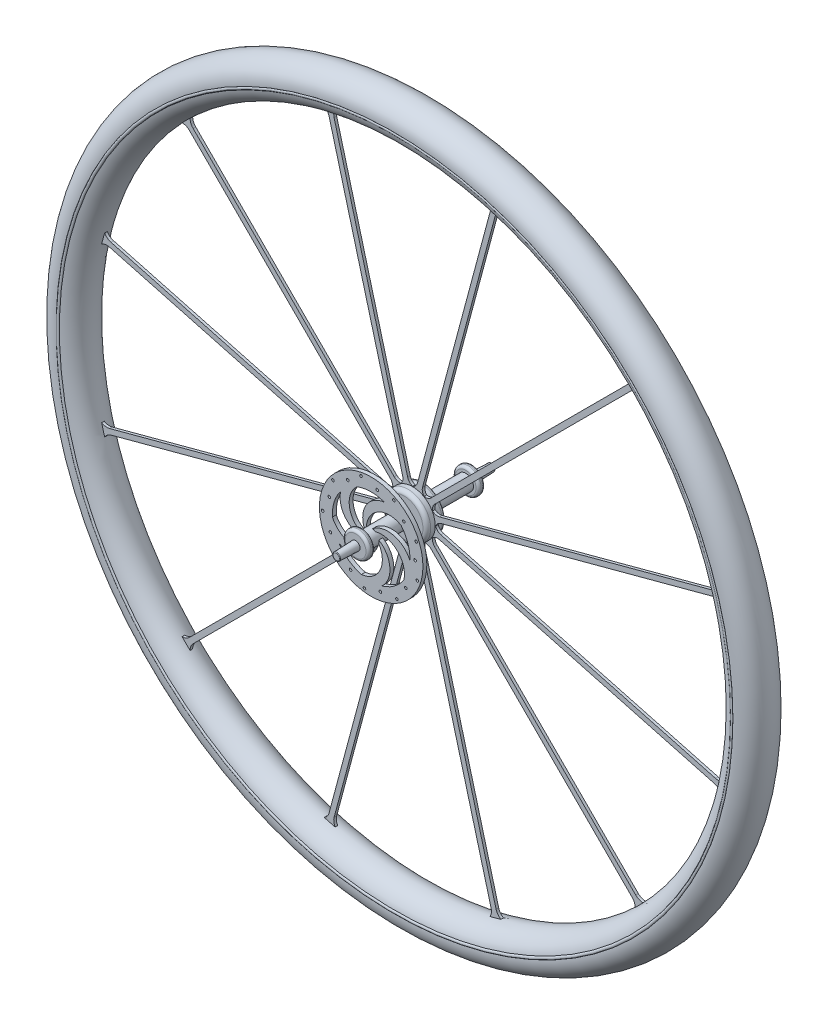
SolidWorks part; units mm, degrees
note: The reader was unsure of these and kept them because the rebuilt part matched: shared geometry of "Sketch1<5>".
ref_plane "Front Plane" through (0, 0, 0) normal (0, 0, 1) x (1, 0, 0)
ref_plane "Top Plane" through (0, 0, 0) normal (0, 1, 0) x (1, 0, 0)
ref_plane "Right Plane" through (0, 0, 0) normal (1, 0, 0) x (0, 0, -1)
sketch "Sketch1" plane through (0, 0, 0) normal (0, 0, 1) x (1, 0, 0)
  circle A2 centre (0, 0) radius 5
  circle A3 centre (0, 0) radius 10
  dimension "D1" = 10
  dimension "D2" = 20
extrude "Boss-Extrude1" add sketch "Sketch1" along normal mid plane 90 contours A3 A2
extrude "Boss-Extrude2" add sketch "Sketch1<5>" along normal mid plane 120 draft 2 contours A2
sketch "Sketch1<5>" plane through (0, 0, 0) normal (0, 0, 1) x (1, 0, 0) same geometry as "Sketch1"
sketch "Sketch4" plane through (0, 0, 0) normal (0, 0, 1) x (1, 0, 0)
  circle A0 centre (0, 0) radius 6
  dimension "D1" = 12
extrude "Cut-Extrude1" cut sketch "Sketch4" against normal mid plane 80 flip side to cut
fillet "Fillet3" radius 2 2 edges at (10, 0, -45) (10, 0, -40)
fillet "Fillet4" radius 2 2 edges at (10, 0, 45) (10, 0, 40)
fillet "Fillet5" radius 0.5 2 edges at (2.9048, 0, 60) (2.9048, 0, -60)
sketch "Sketch5" plane through (0, 0, 0) normal (0, 0, 1) x (1, 0, 0)
  circle A0 centre (0, 0) radius 17.5
  dimension "D1" = 35
extrude "Boss-Extrude3" add sketch "Sketch5" along normal mid plane 15
fillet "Fillet6" radius 3 2 edges at (17.5, 0, -7.5) (17.5, 0, 7.5)
fillet "Fillet7" radius 1 2 edges at (6, 0, -7.5) (6, 0, 7.5)
sketch "Sketch6" plane through (0, 0, 0) normal (0, 0, 1) x (1, 0, 0)
  line L0 (0, 0) -> (2.3864, 17.1683) construction
  line L1 (0, 0) -> (17.5551, 33.1371) construction
  line L8 (5.1628, 37.1429) -> (4.681, 33.6762) construction
  circle A0 centre (0, 0) radius 40
  arc A1 (10.3252, 28.1672) -> (-10.9884, 27.9151) centre (0, 0) ccw
  circle A4 centre (0, 0) radius 34 construction
  circle A5 centre (0, 0) radius 37.5 construction
  circle A6 centre (4.681, 33.6762) radius 1
  circle A7 centre (17.5551, 33.1371) radius 1
  circle A8 centre (25.2325, 22.7886) radius 1
  circle A9 centre (33.9775, 1.238) radius 1
  circle A10 centre (26.824, -20.892) radius 1
  circle A11 centre (7.1193, -33.2463) radius 1
  circle A12 centre (-15.9166, -30.0443) radius 1
  circle A13 centre (-31.505, -12.7843) radius 1
  circle A14 centre (-32.3518, 10.4577) radius 1
  circle A15 centre (-18.0608, 28.8064) radius 1
  circle A16 centre (34.7481, 14.1003) radius 1
  circle A17 centre (35.6821, -11.5342) radius 1
  circle A18 centre (19.92, -31.7717) radius 1
  circle A19 centre (-5.1628, -37.1429) radius 1
  circle A20 centre (-27.83, -25.1345) radius 1
  circle A21 centre (-37.4751, -1.3654) radius 1
  circle A22 centre (-29.5853, 23.0426) radius 1
  circle A23 centre (-7.8521, 36.6687) radius 1
  circle A24 centre (0, 0) radius 6
  circle A27 centre (0, 0) radius 6 construction
  arc A28 (-3.7558, 4.6791) -> (23.1533, 19.0769) centre (14.0997, 3.6528) cw
  arc A29 (-5.2642, 2.8789) -> (10.3252, 28.1672) centre (12.0991, 9.6243) cw
  arc A34 (1.1112, 5.8962) -> (29.9792, -1.1157) centre (12.892, -8.5329) cw
  arc A35 (3.2895, 5.0179) -> (25.2979, -16.125) centre (7.831, -12.2808) cw
  arc A38 (5.951, 0.7652) -> (8.203, -28.8567) centre (-4.1314, -14.8979) cw
  arc A39 (5.7888, -1.5779) -> (-7.5183, -29.0426) centre (-9.2598, -11.2427) cw
  arc A42 (2.5667, -5.4233) -> (-24.9095, -16.7187) centre (-15.4454, -0.6745) cw
  arc A43 (0.2882, -5.9931) -> (-29.9445, -1.8244) centre (-13.5539, 5.3324) cw
  arc A46 (-4.3647, -4.117) -> (-23.5979, 18.524) centre (-5.4144, 14.481) cw
  arc A47 (-5.6107, -2.126) -> (-10.9884, 27.9151) centre (0.883, 14.5383) cw
  arc A50 (29.9792, -1.1157) -> (23.1533, 19.0769) centre (0, 0) ccw
  arc A51 (8.203, -28.8567) -> (25.2979, -16.125) centre (0, 0) ccw
  arc A52 (-24.9095, -16.7187) -> (-7.5183, -29.0426) centre (0, 0) ccw
  arc A53 (-23.5979, 18.524) -> (-29.9445, -1.8244) centre (0, 0) ccw
  point P68 (21.2044, 8.7091)
  point P76 (14.8354, -17.4753)
  point P89 (-12.0356, -19.5094)
  point P102 (-22.2738, 5.4178)
  dimension "D1" = 80
  dimension "D2" = 60
  dimension "D3" = 68
  dimension "D4" = 75
  dimension "D5" = 2
  dimension "D6" = 2
  dimension "D7" = 20
  dimension "D8" = 9
  dimension "D9" = 9
  dimension "D14" = 5
extrude "Boss-Extrude4" add sketch "Sketch6" along normal blind 3 from offset 30
sketch "Sketch8" plane through (0, 0, 0) normal (0, 0, 1) x (1, 0, 0)
  line L0 (0, 0) -> (0, 108.194) construction
  line L1 (-2, 22.0964) -> (-2, 241.7933)
  line L2 (2, 22.0964) -> (2, 241.7933)
  line L3 (-10, 249.7999) -> (10, 249.7999)
  line L4 (14.2103, 17.0387) -> (169.5595, 172.3879)
  line L5 (17.0387, 14.2103) -> (172.3879, 169.5595)
  line L6 (22.0964, 2) -> (241.7933, 2)
  line L7 (22.0964, -2) -> (241.7933, -2)
  line L8 (17.0387, -14.2103) -> (172.3879, -169.5595)
  line L9 (14.2103, -17.0387) -> (169.5595, -172.3879)
  line L10 (2, -22.0964) -> (2, -241.7933)
  line L11 (-2, -22.0964) -> (-2, -241.7933)
  line L12 (-14.2103, -17.0387) -> (-169.5595, -172.3879)
  line L13 (-17.0387, -14.2103) -> (-172.3879, -169.5595)
  line L14 (-22.0964, -2) -> (-241.7933, -2)
  line L15 (-22.0964, 2) -> (-241.7933, 2)
  line L16 (-17.0387, 14.2103) -> (-172.3879, 169.5595)
  line L17 (-14.2103, 17.0387) -> (-169.5595, 172.3879)
  circle A0 centre (0, 0) radius 17.5
  circle A1 centre (0, 0) radius 17.5 construction
  arc A2 (-183.9305, 169.3209) -> (-249.7865, 10.3306) centre (0, 0) ccw
  arc A3 (169.3209, 183.9305) -> (169.5595, 172.3879) centre (163.9026, 178.0447) cw
  arc A5 (-10.3306, 249.7865) -> (-2, 241.7933) centre (-10, 241.7933) cw
  arc A6 (-5.9574, 16.4548) -> (-2, 22.0964) centre (-8, 22.0964) ccw
  arc A7 (5.9574, 16.4548) -> (2, 22.0964) centre (8, 22.0964) cw
  arc A8 (10.3306, 249.7865) -> (2, 241.7933) centre (10, 241.7933) ccw
  arc A9 (183.9305, 169.3209) -> (172.3879, 169.5595) centre (178.0447, 163.9026) ccw
  arc A10 (7.4227, 15.8478) -> (14.2103, 17.0387) centre (9.9676, 21.2814) ccw
  arc A11 (15.8478, 7.4227) -> (17.0387, 14.2103) centre (21.2814, 9.9676) cw
  arc A12 (249.7865, 10.3306) -> (241.7933, 2) centre (241.7933, 10) cw
  arc A13 (249.7865, -10.3306) -> (241.7933, -2) centre (241.7933, -10) ccw
  arc A14 (16.4548, 5.9574) -> (22.0964, 2) centre (22.0964, 8) ccw
  arc A15 (16.4548, -5.9574) -> (22.0964, -2) centre (22.0964, -8) cw
  arc A16 (183.9305, -169.3209) -> (172.3879, -169.5595) centre (178.0447, -163.9026) cw
  arc A17 (169.3209, -183.9305) -> (169.5595, -172.3879) centre (163.9026, -178.0447) ccw
  arc A18 (15.8478, -7.4227) -> (17.0387, -14.2103) centre (21.2814, -9.9676) ccw
  arc A19 (7.4227, -15.8478) -> (14.2103, -17.0387) centre (9.9676, -21.2814) cw
  arc A20 (10.3306, -249.7865) -> (2, -241.7933) centre (10, -241.7933) cw
  arc A21 (-10.3306, -249.7865) -> (-2, -241.7933) centre (-10, -241.7933) ccw
  arc A22 (5.9574, -16.4548) -> (2, -22.0964) centre (8, -22.0964) ccw
  arc A23 (-5.9574, -16.4548) -> (-2, -22.0964) centre (-8, -22.0964) cw
  arc A24 (-169.3209, -183.9305) -> (-169.5595, -172.3879) centre (-163.9026, -178.0447) cw
  arc A25 (-183.9305, -169.3209) -> (-172.3879, -169.5595) centre (-178.0447, -163.9026) ccw
  arc A26 (-7.4227, -15.8478) -> (-14.2103, -17.0387) centre (-9.9676, -21.2814) ccw
  arc A27 (-15.8478, -7.4227) -> (-17.0387, -14.2103) centre (-21.2814, -9.9676) cw
  arc A28 (-249.7865, -10.3306) -> (-241.7933, -2) centre (-241.7933, -10) cw
  arc A29 (-249.7865, 10.3306) -> (-241.7933, 2) centre (-241.7933, 10) ccw
  arc A30 (-16.4548, -5.9574) -> (-22.0964, -2) centre (-22.0964, -8) ccw
  arc A31 (-16.4548, 5.9574) -> (-22.0964, 2) centre (-22.0964, 8) cw
  arc A32 (-183.9305, 169.3209) -> (-172.3879, 169.5595) centre (-178.0447, 163.9026) cw
  arc A33 (-169.3209, 183.9305) -> (-169.5595, 172.3879) centre (-163.9026, 178.0447) ccw
  arc A34 (-15.8478, 7.4227) -> (-17.0387, 14.2103) centre (-21.2814, 9.9676) ccw
  arc A35 (-7.4227, 15.8478) -> (-14.2103, 17.0387) centre (-9.9676, 21.2814) cw
  arc A36 (-249.7865, -10.3306) -> (-183.9305, -169.3209) centre (0, 0) ccw
  arc A37 (169.3209, 183.9305) -> (-169.3209, 183.9305) centre (0, 0) ccw
  arc A38 (249.7865, 10.3306) -> (183.9305, 169.3209) centre (0, 0) ccw
  arc A39 (183.9305, -169.3209) -> (249.7865, -10.3306) centre (0, 0) ccw
  arc A40 (10.3306, -249.7865) -> (169.3209, -183.9305) centre (0, 0) ccw
  arc A41 (-169.3209, -183.9305) -> (-10.3306, -249.7865) centre (0, 0) ccw
  circle A42 centre (0, 0) radius 257.5
  circle A43 centre (0, 0) radius 250
  dimension "D1" = 500
  dimension "D2" = 4
  dimension "D3" = 8
  dimension "D4" = 6
  dimension "D6" = 515
  dimension "D5" = 8
extrude "Boss-Extrude8" add sketch "Sketch8" along normal mid plane 2 contours A33 A43 A32 L16 A34 A0 A35 L17
pattern_circular "CirPattern1" count 12 over 360 about axis through (0, 0, 0) along (0, 0, 1) of "Boss-Extrude8"
sketch "Sketch9" plane through (0, 0, 0) normal (0, 0, 1) x (1, 0, 0)
  circle A0 centre (0, 0) radius 255
  dimension "D1" = 510
sketch "Sketch27" plane through (0, 0, 0) normal (0, 0, 1) x (1, 0, 0)
  arc A0 (-198.3431, 160.2655) -> (-158.6598, 199.6298) centre (-71.274, 71.8514) cw
  circle A1 centre (0, 0) radius 255 construction
ref_plane "Plane1" through (-158.6598, 199.6298, 0) normal (-0.7829, -0.6222, 0) x (0, 0, 1)
sketch "Sketch28" plane through (-158.6598, 199.6298, 0) normal (-0.7829, -0.6222, 0) x (0, 0, 1)
  line L0 (-8.9645, -3.1947) -> (-12.5819, 3.0797)
  line L2 (-59.5174, -255) -> (-86.0016, -255) construction
  line L11 (-14.5809, 4.2191) -> (-13.1521, 3.591)
  line L13 (-59.5174, -252.0784) -> (-59.5174, -257.9216) construction
  line L14 (0, -5.6974) -> (0, 7.9729) construction
  line L15 (0, -5.6974) -> (-4.6328, -5.6974)
  line L16 (0, -510) -> (0, 0) construction
  line L18 (-15, 6.4513) -> (15, 6.4513)
  line L19 (14.5809, 4.2191) -> (13.1521, 3.591)
  line L20 (8.9645, -3.1947) -> (12.5819, 3.0797)
  line L21 (0, -5.6974) -> (4.6328, -5.6974)
  line L27 (5.6574, 2.2165) -> (5.6671, 2.2219)
  line L30 (6.8228, -1.1997) -> (6.8332, -1.1962)
  arc A5 (-13.1521, 3.591) -> (-12.5819, 3.0797) centre (-13.6467, 2.4659) cw
  arc A6 (-14.5809, 4.2191) -> (-15, 6.4513) centre (-14.0272, 5.4785) cw
  arc A8 (-4.6328, -5.6974) -> (-8.9645, -3.1947) centre (-4.6328, -0.6974) cw
  arc A9 (4.6328, -5.6974) -> (8.9645, -3.1947) centre (4.6328, -0.6974) ccw
  arc A10 (14.5809, 4.2191) -> (15, 6.4513) centre (14.0272, 5.4785) ccw
  arc A11 (13.1521, 3.591) -> (12.5819, 3.0797) centre (13.6467, 2.4659) ccw
  point P15 (0, 6.4513)
  dimension "D1" = 5
  dimension "D2" = 15
revolve "Revolve2" add sketch "Sketch28" angle 360 about L2
sketch "Sketch30" plane through (0, 0, 0) normal (0, 0, 1) x (1, 0, 0)
  circle A0 centre (0, 0) radius 262.5
  dimension "D1" = 525
sweep "Sweep2" add path "Sketch30" circular profile diameter 30 parameters "D3"=30
